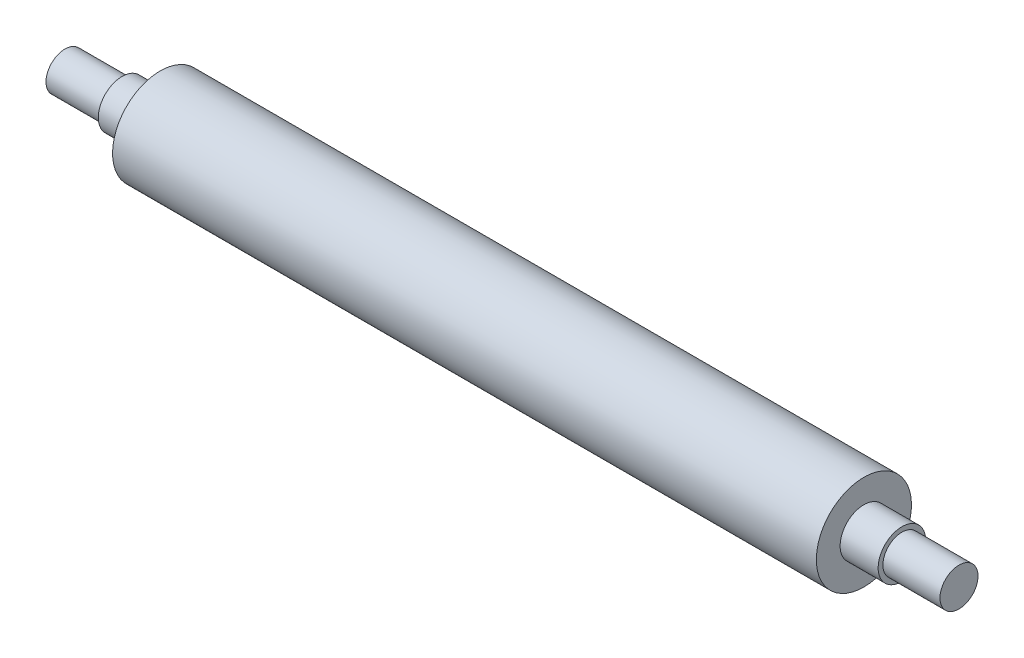
SolidWorks part; units mm, degrees
ref_plane "前视基准面" through (0, 0, 0) normal (0, 0, 1) x (1, 0, 0)
ref_plane "上视基准面" through (0, 0, 0) normal (0, 1, 0) x (1, 0, 0)
ref_plane "右视基准面" through (0, 0, 0) normal (1, 0, 0) x (0, 0, -1)
sketch "草图1" plane through (0, 0, 0) normal (0, 0, 1) x (1, 0, 0)
  line L0 (-230.7094, 0) -> (459.7941, 0) construction
  line L1 (0, 215.5466) -> (0, -189.8195) construction
  line L2 (-185, 25) -> (185, 25)
  line L6 (-235, 10) -> (-235, 0)
  line L7 (-205, 10) -> (-235, 10)
  line L8 (-185, 25) -> (-185, 12.5)
  line L9 (-235, 0) -> (235, 0)
  line L10 (-205, 10) -> (-205, 12.5)
  line L11 (-205, 12.5) -> (-185, 12.5)
  line L12 (235, 10) -> (235, 0)
  line L13 (205, 10) -> (235, 10)
  line L14 (205, 10) -> (205, 12.5)
  line L15 (205, 12.5) -> (185, 12.5)
  line L16 (185, 25) -> (185, 12.5)
  point P17 (0, 25)
  dimension "D1" = 12.5
  dimension "D2" = 10
  dimension "D3" = 25
  dimension "D4" = 370
  dimension "D5" = 30
  dimension "D6" = 410
revolve "旋转1" add sketch "草图1" angle 360 about L9
